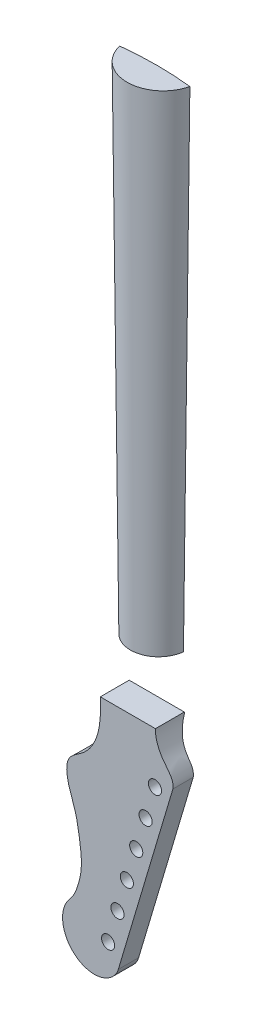
SolidWorks part; units mm, degrees
material "Maple"
ref_plane "Front Plane" through (0, 0, 0) normal (0, 0, 1) x (1, 0, 0)
ref_plane "Top Plane" through (0, 0, 0) normal (0, 1, 0) x (1, 0, 0)
ref_plane "Right Plane" through (0, 0, 0) normal (1, 0, 0) x (0, 0, -1)
sketch "Model" plane through (0, 0, 0) normal (0, 0, 1) x (1, 0, 0)
  line L0 (47.9999, 0) -> (57.149, 660.4)
  line L1 (40.86, 0) -> (46.3494, 660.4)
  line L2 (33.72, 0) -> (35.5498, 660.4)
  line L3 (26.5801, 0) -> (24.7503, 660.4)
  line L4 (19.4401, 0) -> (13.9507, 660.4)
  line L5 (12.3002, 0) -> (3.1511, 660.4)
  line L6 (51.151, 0) -> (60.3001, 660.4)
  line L7 (9.1491, 0) -> (0, 660.4)
  line L8 (51.659, 0) -> (43.9219, 0)
  line L9 (52.1725, 37.0654) -> (44.3327, 37.0654)
  line L10 (52.6572, 72.0505) -> (44.7205, 72.0505)
  line L11 (53.1147, 105.072) -> (45.0865, 105.072)
  line L12 (53.5465, 136.2402) -> (45.4319, 136.2402)
  line L13 (53.954, 165.659) -> (45.7579, 165.659)
  line L14 (54.3387, 193.4267) -> (46.0657, 193.4267)
  line L15 (54.7018, 219.6359) -> (46.3562, 219.6359)
  line L16 (55.0445, 244.3741) -> (46.6304, 244.3741)
  line L17 (55.368, 267.7238) -> (46.8891, 267.7238)
  line L18 (55.6734, 289.763) -> (47.1334, 289.763)
  line L19 (55.9616, 310.5653) -> (47.364, 310.5653)
  line L20 (56.2336, 330.2) -> (47.5816, 330.2)
  line L21 (56.4903, 348.7327) -> (47.787, 348.7327)
  line L22 (56.7327, 366.2252) -> (47.9808, 366.2252)
  line L23 (56.9614, 382.736) -> (48.1638, 382.736)
  line L24 (57.1773, 398.3201) -> (48.3365, 398.3201)
  line L25 (57.3811, 413.0295) -> (48.4996, 413.0295)
  line L26 (57.5734, 426.9133) -> (48.6534, 426.9133)
  line L27 (57.755, 440.0179) -> (48.7987, 440.0179)
  line L28 (57.9263, 452.387) -> (48.9358, 452.387)
  line L29 (58.0881, 464.0619) -> (49.0652, 464.0619)
  line L30 (58.2407, 475.0815) -> (49.1873, 475.0815)
  line L31 (58.3848, 485.4826) -> (49.3026, 485.4826)
  line L32 (58.5208, 495.3) -> (49.4114, 495.3)
  line L33 (44.9379, 0) -> (36.782, 0)
  line L34 (45.3487, 37.0654) -> (36.9874, 37.0654)
  line L35 (45.7365, 72.0505) -> (37.1813, 72.0505)
  line L36 (46.1025, 105.072) -> (37.3643, 105.072)
  line L37 (46.4479, 136.2402) -> (37.537, 136.2402)
  line L38 (46.7739, 165.659) -> (37.7, 165.659)
  line L39 (47.0817, 193.4267) -> (37.8539, 193.4267)
  line L40 (47.3722, 219.6359) -> (37.9991, 219.6359)
  line L41 (47.6464, 244.3741) -> (38.1362, 244.3741)
  line L42 (47.9051, 267.7238) -> (38.2656, 267.7238)
  line L43 (48.1494, 289.763) -> (38.3877, 289.763)
  line L44 (48.38, 310.5653) -> (38.503, 310.5653)
  line L45 (48.5976, 330.2) -> (38.6118, 330.2)
  line L46 (48.803, 348.7327) -> (38.7145, 348.7327)
  line L47 (48.9968, 366.2252) -> (38.8114, 366.2252)
  line L48 (49.1798, 382.736) -> (38.9029, 382.736)
  line L49 (49.3525, 398.3201) -> (38.9893, 398.3201)
  line L50 (49.5156, 413.0295) -> (39.0708, 413.0295)
  line L51 (49.6694, 426.9133) -> (39.1478, 426.9133)
  line L52 (49.8147, 440.0179) -> (39.2204, 440.0179)
  line L53 (49.9518, 452.387) -> (39.2889, 452.387)
  line L54 (50.0812, 464.0619) -> (39.3536, 464.0619)
  line L55 (50.2033, 475.0815) -> (39.4147, 475.0815)
  line L56 (50.3186, 485.4826) -> (39.4723, 485.4826)
  line L57 (50.4274, 495.3) -> (39.5267, 495.3)
  line L58 (37.798, 0) -> (29.6421, 0)
  line L59 (38.0034, 37.0654) -> (29.6421, 37.0654)
  line L60 (38.1973, 72.0505) -> (29.6421, 72.0505)
  line L61 (38.3803, 105.072) -> (29.6421, 105.072)
  line L62 (38.553, 136.2402) -> (29.6421, 136.2402)
  line L63 (38.716, 165.659) -> (29.6421, 165.659)
  line L64 (38.8699, 193.4267) -> (29.6421, 193.4267)
  line L65 (39.0151, 219.6359) -> (29.6421, 219.6359)
  line L66 (39.1522, 244.3741) -> (29.6421, 244.3741)
  line L67 (39.2816, 267.7238) -> (29.6421, 267.7238)
  line L68 (39.4037, 289.763) -> (29.6421, 289.763)
  line L69 (39.519, 310.5653) -> (29.6421, 310.5653)
  line L70 (39.6278, 330.2) -> (29.6421, 330.2)
  line L71 (39.7305, 348.7327) -> (29.6421, 348.7327)
  line L72 (39.8274, 366.2252) -> (29.6421, 366.2252)
  line L73 (39.9189, 382.736) -> (29.6421, 382.736)
  line L74 (40.0053, 398.3201) -> (29.6421, 398.3201)
  line L75 (40.0868, 413.0295) -> (29.6421, 413.0295)
  line L76 (40.1638, 426.9133) -> (29.6421, 426.9133)
  line L77 (40.2364, 440.0179) -> (29.6421, 440.0179)
  line L78 (40.3049, 452.387) -> (29.6421, 452.387)
  line L79 (40.3696, 464.0619) -> (29.6421, 464.0619)
  line L80 (40.4307, 475.0815) -> (29.6421, 475.0815)
  line L81 (40.4883, 485.4826) -> (29.6421, 485.4826)
  line L82 (40.5427, 495.3) -> (29.6421, 495.3)
  line L83 (30.6581, 0) -> (22.5021, 0)
  line L84 (30.6581, 37.0654) -> (22.2967, 37.0654)
  line L85 (30.6581, 72.0505) -> (22.1028, 72.0505)
  line L86 (30.6581, 105.072) -> (21.9199, 105.072)
  line L87 (30.6581, 136.2402) -> (21.7471, 136.2402)
  line L88 (30.6581, 165.659) -> (21.5841, 165.659)
  line L89 (30.6581, 193.4267) -> (21.4302, 193.4267)
  line L90 (30.6581, 219.6359) -> (21.285, 219.6359)
  line L91 (30.6581, 244.3741) -> (21.1479, 244.3741)
  line L92 (30.6581, 267.7238) -> (21.0185, 267.7238)
  line L93 (30.6581, 289.763) -> (20.8964, 289.763)
  line L94 (30.6581, 310.5653) -> (20.7811, 310.5653)
  line L95 (30.6581, 330.2) -> (20.6723, 330.2)
  line L96 (30.6581, 348.7327) -> (20.5696, 348.7327)
  line L97 (30.6581, 366.2252) -> (20.4727, 366.2252)
  line L98 (30.6581, 382.736) -> (20.3812, 382.736)
  line L99 (30.6581, 398.3201) -> (20.2948, 398.3201)
  line L100 (30.6581, 413.0295) -> (20.2133, 413.0295)
  line L101 (30.6581, 426.9133) -> (20.1364, 426.9133)
  line L102 (30.6581, 440.0179) -> (20.0637, 440.0179)
  line L103 (30.6581, 452.387) -> (19.9952, 452.387)
  line L104 (30.6581, 464.0619) -> (19.9305, 464.0619)
  line L105 (30.6581, 475.0815) -> (19.8694, 475.0815)
  line L106 (30.6581, 485.4826) -> (19.8118, 485.4826)
  line L107 (30.6581, 495.3) -> (19.7574, 495.3)
  line L108 (23.5181, 0) -> (15.3622, 0)
  line L109 (23.3127, 37.0654) -> (14.9514, 37.0654)
  line L110 (23.1188, 72.0505) -> (14.5636, 72.0505)
  line L111 (22.9359, 105.072) -> (14.1977, 105.072)
  line L112 (22.7631, 136.2402) -> (13.8522, 136.2402)
  line L113 (22.6001, 165.659) -> (13.5262, 165.659)
  line L114 (22.4462, 193.4267) -> (13.2184, 193.4267)
  line L115 (22.301, 219.6359) -> (12.9279, 219.6359)
  line L116 (22.1639, 244.3741) -> (12.6538, 244.3741)
  line L117 (22.0345, 267.7238) -> (12.395, 267.7238)
  line L118 (21.9124, 289.763) -> (12.1507, 289.763)
  line L119 (21.7971, 310.5653) -> (11.9202, 310.5653)
  line L120 (21.6883, 330.2) -> (11.7025, 330.2)
  line L121 (21.5856, 348.7327) -> (11.4971, 348.7327)
  line L122 (21.4887, 366.2252) -> (11.3033, 366.2252)
  line L123 (21.3972, 382.736) -> (11.1203, 382.736)
  line L124 (21.3108, 398.3201) -> (10.9476, 398.3201)
  line L125 (21.2293, 413.0295) -> (10.7845, 413.0295)
  line L126 (21.1524, 426.9133) -> (10.6307, 426.9133)
  line L127 (21.0797, 440.0179) -> (10.4854, 440.0179)
  line L128 (21.0112, 452.387) -> (10.3483, 452.387)
  line L129 (20.9465, 464.0619) -> (10.2189, 464.0619)
  line L130 (20.8854, 475.0815) -> (10.0968, 475.0815)
  line L131 (20.8278, 485.4826) -> (9.9815, 485.4826)
  line L132 (20.7734, 495.3) -> (9.8727, 495.3)
  line L133 (16.3782, 0) -> (8.6411, 0)
  line L134 (15.9674, 37.0654) -> (8.1276, 37.0654)
  line L135 (15.5796, 72.0505) -> (7.6429, 72.0505)
  line L136 (15.2137, 105.072) -> (7.1854, 105.072)
  line L137 (14.8682, 136.2402) -> (6.7536, 136.2402)
  line L138 (14.5422, 165.659) -> (6.3461, 165.659)
  line L139 (14.2344, 193.4267) -> (5.9614, 193.4267)
  line L140 (13.9439, 219.6359) -> (5.5983, 219.6359)
  line L141 (13.6698, 244.3741) -> (5.2556, 244.3741)
  line L142 (13.411, 267.7238) -> (4.9321, 267.7238)
  line L143 (13.1667, 289.763) -> (4.6267, 289.763)
  line L144 (12.9362, 310.5653) -> (4.3386, 310.5653)
  line L145 (12.7185, 330.2) -> (4.0665, 330.2)
  line L146 (12.5131, 348.7327) -> (3.8098, 348.7327)
  line L147 (12.3193, 366.2252) -> (3.5675, 366.2252)
  line L148 (12.1363, 382.736) -> (3.3387, 382.736)
  line L149 (11.9636, 398.3201) -> (3.1228, 398.3201)
  line L150 (11.8005, 413.0295) -> (2.919, 413.0295)
  line L151 (11.6467, 426.9133) -> (2.7267, 426.9133)
  line L152 (11.5014, 440.0179) -> (2.5451, 440.0179)
  line L153 (11.3643, 452.387) -> (2.3738, 452.387)
  line L154 (11.2349, 464.0619) -> (2.212, 464.0619)
  line L155 (11.1128, 475.0815) -> (2.0594, 475.0815)
  line L156 (10.9975, 485.4826) -> (1.9153, 485.4826)
  line L157 (10.8887, 495.3) -> (1.7793, 495.3)
ref_plane "Plane1" through (0, 37.07, 0) normal (0, 1, 0) x (1, 0, 0)
ref_plane "Plane2" through (0, 413.03, 0) normal (0, 1, 0) x (1, 0, 0)
sketch "Sketch2" plane through (0, 37.07, 0) normal (0, 1, 0) x (1, 0, 0)
  line L0 (22.5021, 0) -> (37.798, 0) construction
  line L4 (30.6581, 0) -> (22.5021, 0) construction
  line L5 (30.6581, 0) -> (22.2967, 0) construction
  line L6 (37.798, 0) -> (29.6421, 0) construction
  line L7 (30.1501, 0) -> (30.1501, -241.3) construction
  line L8 (30.1501, 0) -> (30.1501, -20) construction
  line L9 (30.1501, 0) -> (30.1501, 60) construction
  line L10 (8.7751, 0) -> (51.5251, 0) construction
  arc A0 (51.4416, -0.9412) -> (8.8585, -0.9412) centre (30.1501, -241.3) ccw
  arc A1 (8.7751, 0) -> (8.8585, -0.9412) centre (30.1501, 1.4219) ccw construction
  arc A3 (8.8585, -0.9412) -> (51.4416, -0.9412) centre (30.1501, 1.4219) ccw
  point P17 (30.1501, 0)
  dimension "D1" = 241.3
  dimension "D2" = 20
  dimension "D3" = 60
  dimension "D4" = 42.75
sketch "Sketch4" plane through (0, 413.03, 0) normal (0, 1, 0) x (1, 0, 0)
  line L0 (37.798, 0) -> (22.5021, 0) construction
  line L1 (37.798, 0) -> (29.6421, 0) construction
  line L2 (44.9379, 0) -> (36.782, 0) construction
  line L3 (30.6581, 0) -> (22.5021, 0) construction
  line L4 (30.6581, 0) -> (22.2967, 0) construction
  line L5 (30.1501, 0) -> (30.1501, -241.3) construction
  line L6 (30.1501, 0) -> (30.1501, -22.6) construction
  line L7 (57.2001, 0) -> (3.1001, 0) construction
  circle A0 centre (30.1501, -241.3) radius 241.3 construction
  arc A1 (57.2001, 0) -> (56.8889, -1.4861) centre (30.1501, 4.8875) cw construction
  arc A2 (3.4112, -1.4861) -> (56.8889, -1.4861) centre (30.1501, -241.3) cw
  arc A3 (3.4112, -1.4861) -> (3.1001, 0) centre (30.1501, 4.8875) cw construction
  arc A4 (56.8889, -1.4861) -> (3.4112, -1.4861) centre (30.1501, 4.8875) cw
  point P18 (30.1501, 0)
  dimension "D1" = 241.3
  dimension "D2" = 22.6
  dimension "D3" = 54.1
loft "Loft1" add profiles "Sketch4", "Sketch2" connector at (3.4112, 413.03, 1.4861) connector at (8.8585, 37.07, 0.9412)
sketch "Sketch5" plane through (0, 0, 0) normal (0, 0, 1) x (1, 0, 0)
  line L0 (51.151, 0) -> (51.151, -3.25) construction
  line L1 (51.151, -3.25) -> (9.1491, -3.25) construction
  line L2 (9.1491, -3.25) -> (9.1491, 0) construction
  line L3 (51.151, 0) -> (9.1491, 0) construction
  line L10 (47.9999, 0) -> (47.9999, -42) construction
  line L11 (40.86, 0) -> (40.86, -66) construction
  line L12 (33.72, 0) -> (33.72, -90) construction
  line L13 (26.5801, 0) -> (26.5801, -114) construction
  line L14 (19.4401, 0) -> (19.4401, -138) construction
  line L15 (12.3002, 0) -> (12.3002, -162) construction
  dimension "D1" = 3.25
  dimension "D2" = 42
  dimension "D3" = 66
  dimension "D4" = 90
  dimension "D5" = 114
  dimension "D6" = 138
  dimension "D7" = 162
sketch "Sketch7" plane through (0, 0, 0) normal (0, 0, 1) x (1, 0, 0)
  line L0 (47.9999, -42) -> (50.7999, -42) construction
  line L1 (40.86, -66) -> (43.66, -66) construction
  line L2 (33.72, -90) -> (36.52, -90) construction
  line L3 (26.5801, -114) -> (29.3801, -114) construction
  line L4 (19.4401, -138) -> (22.2401, -138) construction
  line L5 (12.3002, -162) -> (15.1002, -162) construction
  line L6 (50.7999, -42) -> (15.1002, -162) construction
  line L7 (61.8225, -45.2792) -> (26.1228, -165.2792)
  line L8 (61.8225, -45.2792) -> (64.4679, -36.3869)
  line L9 (26.1228, -165.2792) -> (22.17, -178.5661)
  line L10 (9.1491, -3.25) -> (9.1491, -15.8462)
  line L11 (51.151, -3.25) -> (9.1491, -3.25)
  circle A0 centre (50.7999, -42) radius 5
  circle A6 centre (43.66, -66) radius 5
  circle A7 centre (36.52, -90) radius 5
  circle A8 centre (29.3801, -114) radius 5
  circle A9 centre (22.2401, -138) radius 5
  circle A10 centre (15.1002, -162) radius 5
  circle A11 centre (50.7999, -42) radius 7 construction
  circle A12 centre (43.66, -66) radius 7 construction
  circle A13 centre (36.52, -90) radius 7 construction
  circle A14 centre (29.3801, -114) radius 7 construction
  circle A15 centre (22.2401, -138) radius 7 construction
  circle A16 centre (15.1002, -162) radius 7 construction
  arc A17 (-14.3635, -148.6324) -> (-8.2654, -137.2309) centre (-37.1467, -129.1151) ccw
  ellipse E0 centre (2.8278, -165.1094) end of major axis (14.6602, -186.0066) minor radius 21.8622 (-14.3635, -148.6324) -> (22.17, -178.5661) ccw
  spline S2 degree 3 poles (51.151, -3.25) (50.9376, -10.7673) (56.4838, -22.0007) (65.2963, -30.5662) (64.4679, -36.3869) knots 0 0 0 0 0.598162 1 1 1 1
  spline S3 degree 3 poles (9.1491, -15.8462) (8.8138, -24.4005) (5.6701, -42.7139) (-21.2448, -56.6572) (-10.2412, -86.8972) (-8.6046, -92.571) (-3.491, -123.9198) (-6.8296, -132.1214) (-8.2654, -137.2309) knots 0 0 0 0 0.241122 0.31589 0.476811 0.625348 0.735304 0.929975 0.929975 0.929975 0.929975
  point P32 (-6.6579, -142.6678)
  point P33 (0, 0)
  point P37 (-16.1964, -175.8813)
  point P38 (-6.0074, -139.1839)
  point P42 (-5.3298, -116.3824)
  point P43 (-8.2654, -137.2309)
  point P45 (-14.3635, -55.311)
  point P48 (-7.824, -97.8428)
  point P49 (-11.9565, -82.418)
  point P50 (4.6582, -35.333)
  dimension "D7" = 10
  dimension "D8" = 10
  dimension "D9" = 10
  dimension "D10" = 10
  dimension "D11" = 10
  dimension "D12" = 10
  dimension "D13" = 11.5
  dimension "D14" = 30
  dimension "D1" = 2.8
  dimension "D2" = 2.8
  dimension "D3" = 2.8
  dimension "D4" = 2.8
  dimension "D5" = 2.8
  dimension "D6" = 2.8
extrude "Boss-Extrude1" add sketch "Sketch7" along normal blind 22 separate body
sketch "Sketch9" plane through (0, 0, 0) normal (1, 0, 0) x (0, 0, -1)
  line L0 (0, -188.6196) -> (-6.5, -188.6196)
  line L1 (-22, -188.6196) -> (0, -188.6196) construction
  line L2 (-6.5, -188.6196) -> (-6.5, -21.6831)
  line L3 (-22, -3.25) -> (0, -3.25) construction
  line L4 (-6.5, -3.25) -> (0, -3.25) construction
  line L6 (0, -3.25) -> (0, -4.75) construction
  line L7 (0, -4.75) -> (-6.5, -21.6831)
  line L8 (-6.5, -21.6831) -> (-6.5, -3.25) construction
  line L9 (0, -4.75) -> (0, -188.6196)
  point P10 (-6.5, -21.6093)
  point P13 (-2.4341, -19.6214)
  point P14 (0, -4.138)
  dimension "D1" = 6.5
  dimension "D2" = 1.5
extrude "Cut-Extrude1" cut sketch "Sketch9" against normal blind 47 and the other way blind 89 contours L9 L7 L2 L0 region at (0, -100.8499, 3.1977)
fillet "Fillet1" radius 35 1 edges at (33.0985, -21.6831, 6.5)
fillet "Fillet2" radius 15 1 edges at (22.17, -178.5661, 14.25)
